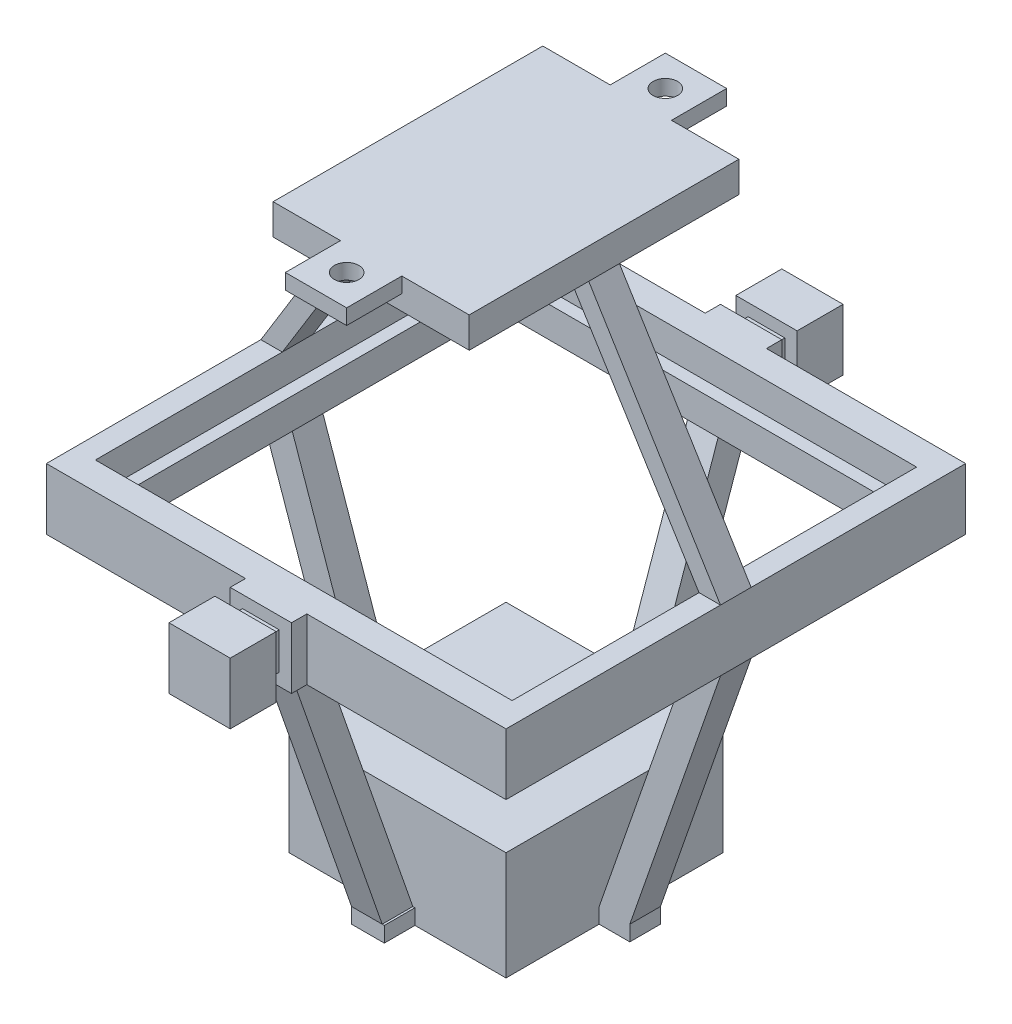
SolidWorks part; units mm, degrees
ref_plane "Front Plane" through (0, 0, 0) normal (0, 0, 1) x (1, 0, 0)
ref_plane "Top Plane" through (0, 0, 0) normal (0, 1, 0) x (1, 0, 0)
ref_plane "Right Plane" through (0, 0, 0) normal (1, 0, 0) x (0, 0, -1)
sketch "Sketch2" plane through (0, 0, 0) normal (0, 1, 0) x (1, 0, 0)
  line L1 (-37.5, 37.5) -> (37.5, 37.5)
  line L2 (-37.5, 37.5) -> (-37.5, -37.5)
  line L3 (-37.5, -37.5) -> (37.5, -37.5)
  line L4 (37.5, 37.5) -> (37.5, -37.5)
  line L5 (-37.5, 37.5) -> (37.5, -37.5) construction
  line L6 (-37.5, -37.5) -> (37.5, 37.5) construction
  point P0 (0, 0)
extrude "Boss-Extrude1" add sketch "Sketch2" along normal blind 5
extrude "Boss-Extrude2" add sketch "Sketch2<2>" against normal blind 5
sketch "Sketch2<2>" plane through (0, 0, 0) normal (0, 1, 0) x (1, 0, 0) same geometry as "Sketch2"
sketch "Sketch4" plane through (0, 5, 0) normal (0, 1, 0) x (1, 0, 0)
  line L1 (-34, 33) -> (34, 33)
  line L2 (-34, 33) -> (-34, -33)
  line L3 (-34, -33) -> (34, -33)
  line L4 (34, 33) -> (34, -33)
  line L5 (-34, 33) -> (34, -33) construction
  line L6 (-34, -33) -> (34, 33) construction
  point P0 (0, 0)
extrude "Cut-Extrude1" cut sketch "Sketch4" against normal blind 5
sketch "Sketch5" plane through (0, 0, 0) normal (0, 1, 0) x (1, 0, 0)
  line L1 (-32, 31) -> (32, 31)
  line L2 (-32, 31) -> (-32, -31)
  line L3 (-32, -31) -> (32, -31)
  line L4 (32, 31) -> (32, -31)
  line L5 (-32, 31) -> (32, -31) construction
  line L6 (-32, -31) -> (32, 31) construction
  point P0 (0, 0)
extrude "Cut-Extrude2" cut sketch "Sketch5" against normal blind 5
sketch "Sketch6" plane through (0, 0, 37.5) normal (0, 0, 1) x (1, 0, 0)
  line L0 (-37.5, -5) -> (37.5, -5) construction
  line L1 (-5, 5) -> (5, 5)
  line L2 (-5, 5) -> (-5, -5)
  line L3 (-5, -5) -> (5, -5)
  line L4 (5, 5) -> (5, -5)
  line L5 (-5, 5) -> (5, -5) construction
  line L6 (-5, -5) -> (5, 5) construction
  point P0 (0, 0)
extrude "Boss-Extrude3" add sketch "Sketch6" along normal blind 2.5
sketch "Sketch7" plane through (0, 0, 40) normal (0, 0, 1) x (1, 0, 0)
  line L1 (-3, 3) -> (3, 3)
  line L2 (-3, 3) -> (-3, -3)
  line L3 (-3, -3) -> (3, -3)
  line L4 (3, 3) -> (3, -3)
  line L5 (-3, 3) -> (3, -3) construction
  line L6 (-3, -3) -> (3, 3) construction
  point P0 (0, 0)
extrude "Boss-Extrude4" add sketch "Sketch7" along normal blind 2.5
sketch "Sketch8" plane through (0, 0, 42.5) normal (0, 0, 1) x (1, 0, 0)
  line L1 (-5, 5) -> (5, 5)
  line L2 (-5, 5) -> (-5, -5)
  line L3 (-5, -5) -> (5, -5)
  line L4 (5, 5) -> (5, -5)
  line L5 (-5, 5) -> (5, -5) construction
  line L6 (-5, -5) -> (5, 5) construction
  point P0 (0, 0)
extrude "Boss-Extrude5" add sketch "Sketch8" along normal blind 7.5
sketch "Sketch9" plane through (0, 0, -37.5) normal (0, 0, -1) x (-1, 0, 0)
  line L1 (-5, 5) -> (5, 5)
  line L2 (-5, 5) -> (-5, -5)
  line L3 (-5, -5) -> (5, -5)
  line L4 (5, 5) -> (5, -5)
  line L5 (-5, 5) -> (5, -5) construction
  line L6 (-5, -5) -> (5, 5) construction
  point P0 (0, 0)
extrude "Boss-Extrude6" add sketch "Sketch9" along normal blind 2.5
sketch "Sketch10" plane through (0, 0, -40) normal (0, 0, -1) x (-1, 0, 0)
  line L1 (-3, 3) -> (3, 3)
  line L2 (-3, 3) -> (-3, -3)
  line L3 (-3, -3) -> (3, -3)
  line L4 (3, 3) -> (3, -3)
  line L5 (-3, 3) -> (3, -3) construction
  line L6 (-3, -3) -> (3, 3) construction
  point P0 (0, 0)
extrude "Boss-Extrude7" add sketch "Sketch10" along normal blind 2.5
sketch "Sketch11" plane through (0, 0, -42.5) normal (0, 0, -1) x (-1, 0, 0)
  line L1 (-5, 5) -> (5, 5)
  line L2 (-5, 5) -> (-5, -5)
  line L3 (-5, -5) -> (5, -5)
  line L4 (5, 5) -> (5, -5)
  line L5 (-5, 5) -> (5, -5) construction
  line L6 (-5, -5) -> (5, 5) construction
  point P0 (0, 0)
extrude "Boss-Extrude8" add sketch "Sketch11" along normal blind 7.5
ref_plane "Plane1" through (0, 50, 0) normal (0, 1, 0) x (1, 0, 0)
ref_plane "Plane3" through (0, 45, 0) normal (0, 1, 0) x (1, 0, 0)
ref_plane "Plane4" through (0, -50, 0) normal (0, 1, 0) x (1, 0, 0)
sketch "Sketch14" plane through (0, -50, 0) normal (0, 1, 0) x (1, 0, 0)
  line L1 (17.7, 17.7) -> (-17.7, 17.7)
  line L2 (17.7, 17.7) -> (17.7, -17.7)
  line L3 (17.7, -17.7) -> (-17.7, -17.7)
  line L4 (-17.7, 17.7) -> (-17.7, -17.7)
  line L5 (17.7, 17.7) -> (-17.7, -17.7) construction
  line L6 (17.7, -17.7) -> (-17.7, 17.7) construction
  point P0 (0, 0)
extrude "Boss-Extrude9" add sketch "Sketch14" along normal blind 17.7 separate body
sketch "Sketch15" plane through (0, -50, 0) normal (0, -1, 0) x (1, 0, 0)
  line L1 (-12.7, 12.7) -> (12.7, 12.7)
  line L2 (-12.7, 12.7) -> (-12.7, -12.7)
  line L3 (-12.7, -12.7) -> (12.7, -12.7)
  line L4 (12.7, 12.7) -> (12.7, -12.7)
  line L5 (-12.7, 12.7) -> (12.7, -12.7) construction
  line L6 (-12.7, -12.7) -> (12.7, 12.7) construction
  point P0 (0, 0)
extrude "Cut-Extrude3" cut sketch "Sketch15" against normal blind 12.7
sketch "Sketch16" plane through (0, 45, 0) normal (0, 1, 0) x (1, 0, 0)
  line L1 (-16, 22) -> (16, 22)
  line L2 (-16, 22) -> (-16, -22)
  line L3 (-16, -22) -> (16, -22)
  line L4 (16, 22) -> (16, -22)
  line L5 (-16, 22) -> (16, -22) construction
  line L6 (-16, -22) -> (16, 22) construction
  point P0 (0, 0)
extrude "Boss-Extrude10" add sketch "Sketch16" against normal blind 5 separate body
sketch "Sketch18" plane through (0, 45, 0) normal (0, 1, 0) x (1, 0, 0)
  line L21 (16, 22) -> (-16, 22) construction
  line L22 (-5, 22) -> (5, 22)
  line L23 (-5, 22) -> (-5, 31)
  line L24 (-5, 31) -> (5, 31)
  line L25 (5, 22) -> (5, 31)
  line L26 (32, 31) -> (-32, 31) construction
  line L33 (-16, -22) -> (16, -22) construction
  line L34 (-5, -22) -> (5, -22)
  line L35 (-5, -22) -> (-5, -31)
  line L36 (-5, -31) -> (5, -31)
  line L37 (5, -22) -> (5, -31)
  line L38 (-32, -31) -> (32, -31) construction
extrude "Boss-Extrude12" add sketch "Sketch18" against normal blind 2.5
sketch "Sketch21" plane through (0, 0, 0) normal (0, 0, 1) x (1, 0, 0)
  line L0 (-37.5, 5) -> (-34, 5)
  line L1 (-37.5, 5) -> (-5, 5) construction
  line L2 (-37.5, 5) -> (-16, 40)
  line L3 (-34, 5) -> (-12.4348, 40)
  line L4 (-16, 40) -> (16, 40) construction
  line L5 (-12.4348, 40) -> (-16, 40)
  line L6 (37.5, 5) -> (34, 5)
  line L7 (5, 5) -> (37.5, 5) construction
  line L8 (37.5, 5) -> (16, 40)
  line L9 (34, 5) -> (12.2456, 40)
  line L10 (12.2456, 40) -> (16, 40)
extrude "Boss-Extrude13" add sketch "Sketch21" along normal blind 2.5
extrude "Boss-Extrude14" add sketch "Sketch21<2>" against normal blind 2.5
sketch "Sketch21<2>" plane through (0, 0, 0) normal (0, 0, 1) x (1, 0, 0) same geometry as "Sketch21"
sketch "Sketch31" plane through (0, 45, 0) normal (0, 1, 0) x (1, 0, 0)
  line L0 (0, -52.25) -> (0, 52.25) construction
  circle A0 centre (0, 26) radius 2
  circle A1 centre (0, -26) radius 2
extrude "Charger Support Holes" cut sketch "Sketch31" against normal blind 2.5
sketch "Sketch27" plane through (0, -50, 0) normal (0, -1, 0) x (-1, 0, 0)
  line L0 (-17.7, -17.7) -> (-17.7, 17.7) construction
  line L1 (-12.2456, -2.5) -> (-34, -2.5) construction
  line L2 (-17.7, -2.5) -> (-22.7, -2.5)
  line L3 (-17.7, -2.5) -> (-17.7, 2.5)
  line L4 (-17.7, 2.5) -> (-22.7, 2.5)
  line L5 (-22.7, -2.5) -> (-22.7, 2.5)
  line L6 (-12.2456, 2.5) -> (-34, 2.5) construction
  line L21 (17.7, 17.7) -> (17.7, -17.7) construction
  line L22 (34, -2.5) -> (12.4348, -2.5) construction
  line L23 (34, 2.5) -> (12.4348, 2.5) construction
  line L26 (17.7, -2.5) -> (22.7, -2.5)
  line L27 (17.7, -2.5) -> (17.7, 2.5)
  line L28 (17.7, 2.5) -> (22.7, 2.5)
  line L29 (22.7, -2.5) -> (22.7, 2.5)
  line L33 (17.7, -17.7) -> (-17.7, -17.7) construction
  line L34 (2.5, -17.7) -> (-2.8444, -17.7)
  line L35 (2.5, -17.7) -> (2.5, -22.7)
  line L36 (2.5, -22.7) -> (-2.8444, -22.7)
  line L37 (-2.8444, -17.7) -> (-2.8444, -22.7)
  line L39 (-17.7, 17.7) -> (17.7, 17.7) construction
  line L44 (2.5, 17.7) -> (-2.5, 17.7)
  line L45 (2.5, 17.7) -> (2.5, 22.7)
  line L46 (2.5, 22.7) -> (-2.5, 22.7)
  line L47 (-2.5, 17.7) -> (-2.5, 22.7)
extrude "Eyebolt Bolt Supports" add sketch "Sketch27" against normal blind 2.5
sketch "Sketch28" plane through (0, 0, 0) normal (0, 0, 1) x (1, 0, 0)
  line L0 (22.7, -47.5) -> (37.5, -5)
  line L1 (37.5, -5) -> (32.5, -5)
  line L2 (5, -5) -> (37.5, -5) construction
  line L3 (32.5, -5) -> (17.7, -47.5)
  line L4 (17.7, -47.5) -> (22.7, -47.5)
  line L5 (-22.7, -47.5) -> (-37.5, -5)
  line L6 (-37.5, -5) -> (-32.5, -5)
  line L7 (-32.5, -5) -> (-17.7, -47.5)
  line L8 (-17.7, -47.5) -> (-22.7, -47.5)
extrude "Boss-Extrude15" add sketch "Sketch28" along normal blind 2.5
extrude "Boss-Extrude16" add sketch "Sketch28<2>" against normal blind 2.5
sketch "Sketch28<2>" plane through (0, 0, 0) normal (0, 0, 1) x (1, 0, 0) same geometry as "Sketch28"
sketch "Sketch30" plane through (0, 0, 0) normal (1, 0, 0) x (0, 0, -1)
  line L0 (22.7, -47.5) -> (37.5, -5)
  line L1 (37.5, -5) -> (32.5, -5)
  line L2 (2.5, -5) -> (37.5, -5) construction
  line L3 (22.7, -47.5) -> (17.7, -47.5)
  line L4 (17.7, -47.5) -> (32.5, -5)
  line L5 (-37.5, -5) -> (-22.7, -47.5)
  line L7 (-22.7, -47.5) -> (-17.7, -47.5)
  line L8 (-17.7, -47.5) -> (-32.5, -5)
  line L9 (-37.5, -5) -> (-2.5, -5) construction
  line L10 (-32.5, -5) -> (-37.5, -5)
extrude "Boss-Extrude17" add sketch "Sketch30" along normal blind 2.5
extrude "Boss-Extrude18" add sketch "Sketch30<2>" against normal blind 2.5
sketch "Sketch30<2>" plane through (0, 0, 0) normal (1, 0, 0) x (0, 0, -1) same geometry as "Sketch30"
